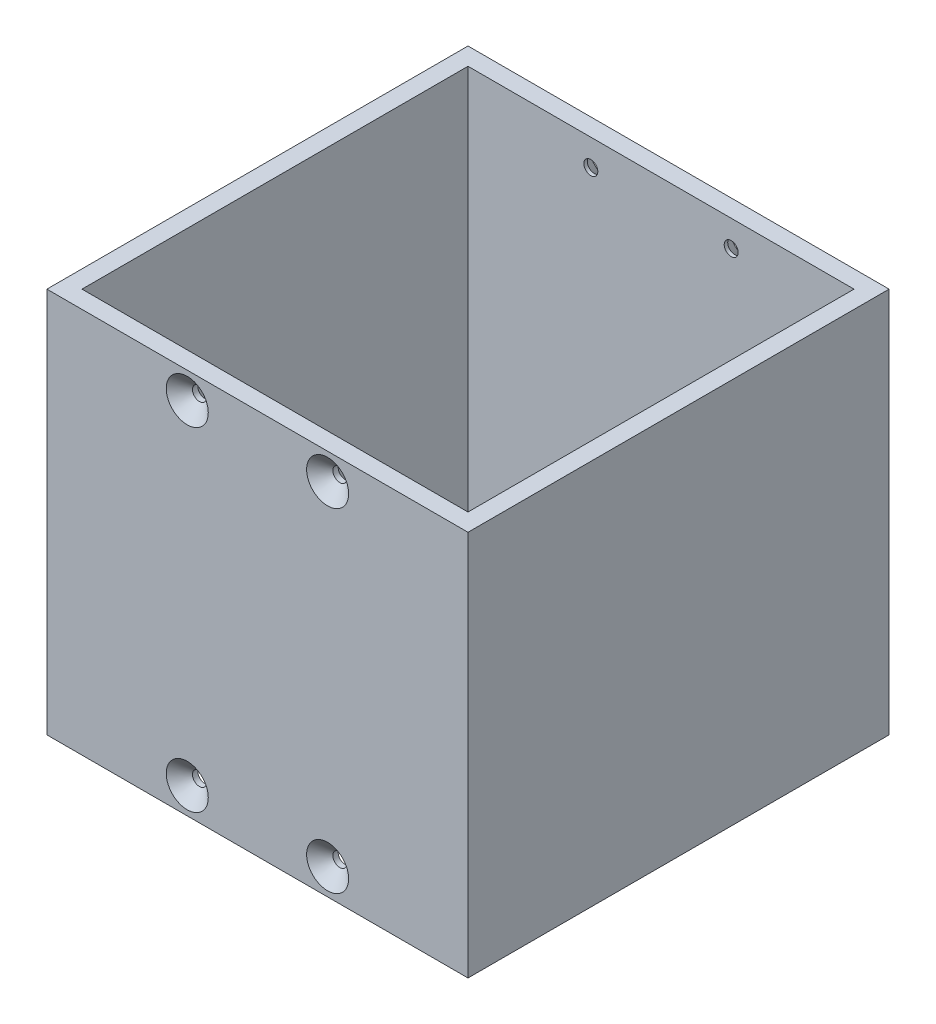
SolidWorks part; units mm, degrees
material "6061-T6 (SS)"
ref_plane "Front Plane" through (0, 0, 0) normal (0, 0, 1) x (1, 0, 0)
ref_plane "Top Plane" through (0, 0, 0) normal (0, 1, 0) x (1, 0, 0)
ref_plane "Right Plane" through (0, 0, 0) normal (1, 0, 0) x (0, 0, -1)
sketch "Sketch1" plane through (0, 0, 0) normal (0, 1, 0) x (1, 0, 0)
  line L1 (-38.1, -38.1) -> (38.1, -38.1)
  line L2 (-38.1, -38.1) -> (-38.1, 38.1)
  line L3 (-38.1, 38.1) -> (38.1, 38.1)
  line L4 (38.1, -38.1) -> (38.1, 38.1)
  line L5 (-38.1, -38.1) -> (38.1, 38.1) construction
  line L6 (-38.1, 38.1) -> (38.1, -38.1) construction
  line L7 (-34.925, -34.925) -> (34.925, -34.925)
  line L8 (-34.925, -34.925) -> (-34.925, 34.925)
  line L9 (-34.925, 34.925) -> (34.925, 34.925)
  line L10 (34.925, -34.925) -> (34.925, 34.925)
  line L11 (-34.925, -34.925) -> (34.925, 34.925) construction
  line L12 (-34.925, 34.925) -> (34.925, -34.925) construction
  point P0 (0, 0)
  point P6 (0, 0)
  dimension "D1" = 76.2
  dimension "D2" = 76.2
  dimension "D3" = 3.175
extrude "Boss-Extrude1" add sketch "Sketch1" along normal blind 9.525
sketch "Sketch2" plane through (0, 0, 38.1) normal (0, 0, 1) x (1, 0, 0)
  line L0 (-38.1, 0) -> (38.1, 0) construction
  circle A0 centre (-12.7, 4.7625) radius 1.2637
  circle A1 centre (12.7, 4.7625) radius 1.2637
  dimension "D4" = 2.5273
  dimension "D1" = 4.7625
  dimension "D2" = 12.7
  dimension "D3" = 12.7
extrude "Cut-Extrude1" cut sketch "Sketch2" against normal through all
chamfer "Chamfer1" distance 2.54 angle 41 4 edges at (-11.4363, 4.7625, -38.1) (13.9636, 4.7625, -38.1) (13.9636, 4.7625, 38.1) (-11.4363, 4.7625, 38.1) first distance on face at (-11.4363, 4.7625, -34.925) first distance on face at (13.9636, 4.7625, -34.925) first distance on face at (13.9636, 4.7625, 38.1)
sketch "Sketch3" plane through (0, 9.525, 0) normal (0, 1, 0) x (1, 0, 0)
  line L0 (-34.925, 34.925) -> (-34.925, -34.925) construction
  line L1 (-34.925, -34.925) -> (34.925, -34.925) construction
  line L2 (34.925, 34.925) -> (-34.925, 34.925) construction
  line L3 (34.925, -34.925) -> (34.925, 34.925) construction
  line L4 (38.1, -38.1) -> (38.1, 38.1)
  line L5 (38.1, 38.1) -> (-38.1, 38.1)
  line L6 (-38.1, 38.1) -> (-38.1, -38.1)
  line L7 (-38.1, -38.1) -> (38.1, -38.1)
  line L8 (38.1, -38.1) -> (38.1, 38.1)
  line L9 (38.1, 38.1) -> (-38.1, 38.1)
  line L10 (-38.1, 38.1) -> (-38.1, -38.1)
  line L11 (-38.1, -38.1) -> (38.1, -38.1)
  line L12 (-34.925, 34.925) -> (-34.925, -34.925)
  line L13 (-34.925, -34.925) -> (34.925, -34.925)
  line L14 (34.925, 34.925) -> (-34.925, 34.925)
  line L15 (34.925, -34.925) -> (34.925, 34.925)
  dimension "D1" = 0
extrude "Boss-Extrude2" add sketch "Sketch3" along normal blind 25.4
mirror "Mirror2" about plane through (0, 34.925, 0) normal (0, 1, 0) of bodies 103
equation "\"D3@Sketch2\"=\"D2@Sketch2\""
equation "\"D1@Sketch1\"=\"D2@Sketch1\""
